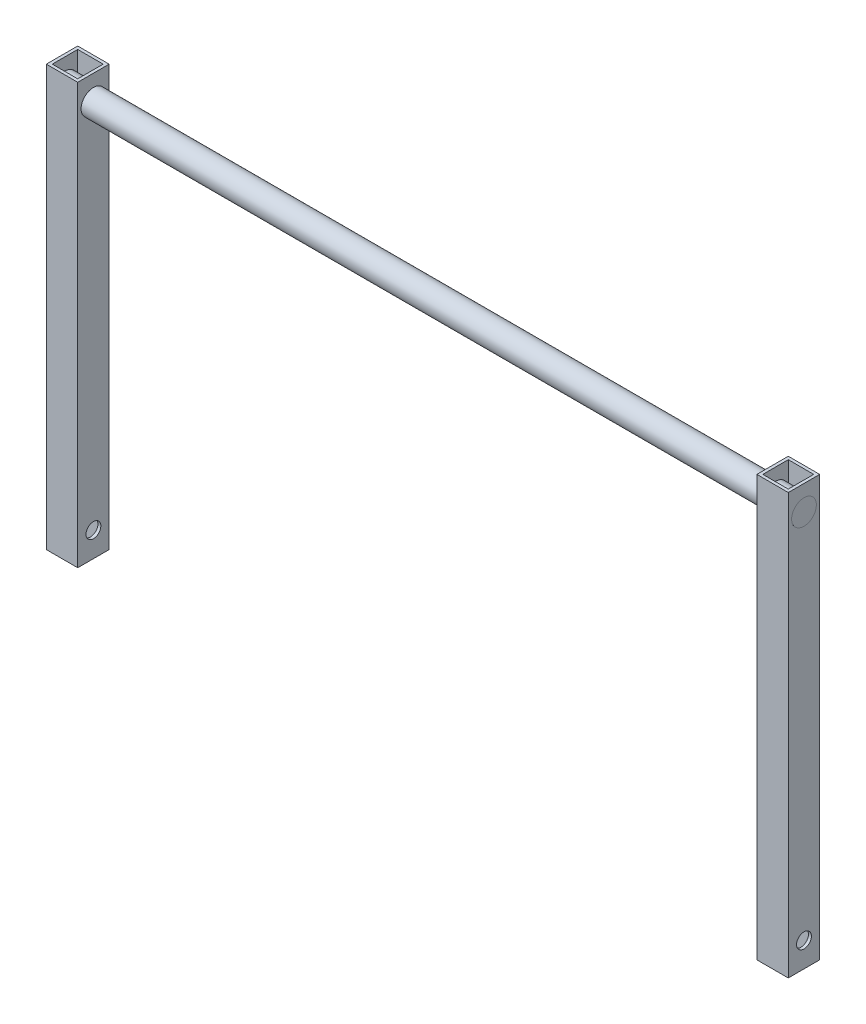
SolidWorks part; units mm, degrees
ref_plane "Front Plane" through (0, 0, 0) normal (0, 0, 1) x (1, 0, 0)
ref_plane "Top Plane" through (0, 0, 0) normal (0, 1, 0) x (1, 0, 0)
ref_plane "Right Plane" through (0, 0, 0) normal (1, 0, 0) x (0, 0, -1)
sketch "Sketch1" plane through (0, 0, 0) normal (1, 0, 0) x (0, 0, -1)
  circle A0 centre (0, 0) radius 5
  dimension "D1" = 10
extrude "Boss-Extrude1" add sketch "Sketch1" along normal mid plane 300
sketch "Sketch2" plane through (-150, 0, 0) normal (-1, 0, 0) x (0, 0, 1)
  line L1 (-6.35, 10) -> (6.35, 10)
  line L2 (-6.35, 10) -> (-6.35, -160)
  line L3 (-6.35, -160) -> (6.35, -160)
  line L4 (6.35, 10) -> (6.35, -160)
  circle A0 centre (0, -150) radius 3
  point P4 (0, 10)
  circle M5 centre (0, 0) radius 5
  dimension "D4" = 6
  dimension "D1" = 12.7
  dimension "D2" = 10
  dimension "D3" = 170
  dimension "D5" = 150
extrude "Boss-Extrude2" add sketch "Sketch2" against normal blind 12.7 separate body contours L4 L1 L2 L3 A0 M5 | A0 | M5 region at (-150, -76.837, 0) region at (-150, -150, 0) region at (-150, 0, 0)
shell "Shell1" thickness 1.2 removed face at (-143.65, 10, 0) removed face at (-143.65, -160, 0)
extrude "Cut-Extrude1" cut sketch "Sketch2<3>" against normal through all contours A0 | M5 region at (-150, -150, 0) region at (-150, 0, 0)
sketch "Sketch2<3>" plane through (-150, 0, 0) normal (-1, 0, 0) x (0, 0, 1) same geometry as "Sketch2"
mirror "Mirror1" about plane through (0, 0, 0) normal (1, 0, 0) of bodies 104 102
